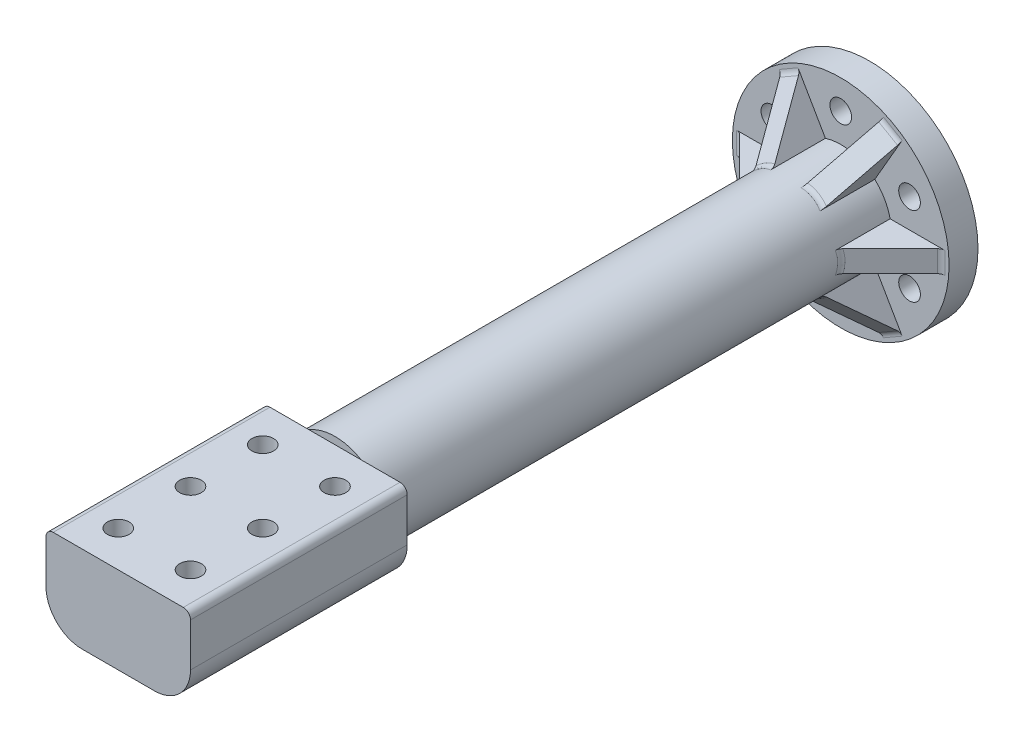
SolidWorks part; units mm, degrees
ref_plane "前视基准面" through (0, 0, 0) normal (0, 0, 1) x (1, 0, 0)
ref_plane "上视基准面" through (0, 0, 0) normal (0, 1, 0) x (1, 0, 0)
ref_plane "右视基准面" through (0, 0, 0) normal (1, 0, 0) x (0, 0, -1)
sketch "草图1" plane through (0, 0, 0) normal (0, 0, 1) x (1, 0, 0)
  circle A1 centre (0, 0) radius 15
  circle A3 centre (0, 11) radius 1.5
  circle A4 centre (9.5263, 5.5) radius 1.5
  circle A5 centre (9.5263, -5.5) radius 1.5
  circle A6 centre (0, -11) radius 1.5
  circle A7 centre (-9.5263, -5.5) radius 1.5
  circle A8 centre (-9.5263, 5.5) radius 1.5
  dimension "D1" = 3
  dimension "D2" = 30
  dimension "D3" = 11
  dimension "D4" = 6
extrude "凸台-拉伸1" add sketch "草图1" against normal blind 4
sketch "草图14" plane through (0, 0, 0) normal (0, 0, 1) x (1, 0, 0)
  circle A1 centre (0, 0) radius 7
  dimension "D1" = 14
extrude "凸台-拉伸2" add sketch "草图14" along normal blind 70
sketch "草图15" plane through (0, 0, 70) normal (0, 0, 1) x (1, 0, 0)
  line L12 (10, -6) -> (-10, -6)
  line L13 (10, -6) -> (10, 6)
  line L14 (10, 6) -> (-10, 6)
  line L15 (-10, -6) -> (-10, 6)
  line L16 (10, -6) -> (-10, 6) construction
  line L17 (10, 6) -> (-10, -6) construction
  point P0 (0, 0)
  dimension "D1" = 20
  dimension "D2" = 12
extrude "凸台-拉伸3" add sketch "草图15" along normal blind 30
sketch "草图19" plane through (0, 6, 0) normal (0, 1, 0) x (1, 0, 0)
  line L0 (-3.6056, -70) -> (-10, -70) construction
  line L1 (-10, -100) -> (-10, -70) construction
  circle A0 centre (-5, -75) radius 1.5
  circle A1 centre (5, -75) radius 1.5
  circle A2 centre (-5, -85) radius 1.5
  circle A3 centre (5, -85) radius 1.5
  circle A4 centre (-5, -95) radius 1.5
  circle A5 centre (5, -95) radius 1.5
  dimension "D1" = 3
  dimension "D2" = 5
  dimension "D3" = 5
  dimension "D4" = 2
  dimension "D5" = 2
  dimension "D6" = 2
extrude "切除-拉伸1" cut sketch "草图19" against normal up to next
sketch "草图21" plane through (0, 0, 0) normal (0, 1, 0) x (1, 0, 0)
  line L0 (-14, 0) -> (-7, -7)
  line L1 (-15, 0) -> (15, 0) construction
  line L2 (-7, 0) -> (-7, -70) construction
  line L3 (-15, 4) -> (-15, 0) construction
  dimension "D1" = 1
  dimension "D2" = 45
rib "筋1" sketch "草图21" sketch "草图21" thickness 3 extrusion direction parallel to sketch draft on no parameters "D1"=3
pattern_circular "阵列(圆周)1" count 6 over 360 about axis through (0, 0, 0) along (0, 0, 1) of "筋1"
fillet "圆角1" radius 5 2 edges at (-10, -6, 85) (10, -6, 85)
fillet "圆角2" radius 1 14 edges at (-10, 6, 85) (10, 6, 85) (-7, -12.1244, 0) (7, -12.1244, 0) (14, 0, 0) (-14, 0, 0) (-7, 12.1244, 0) (7, 12.1244, 0) (7, 0, 7) (3.5, 6.0622, 7) (-3.5, 6.0622, 7) (-7, 0, 7) (3.5, -6.0622, 7) (-3.5, -6.0622, 7)
